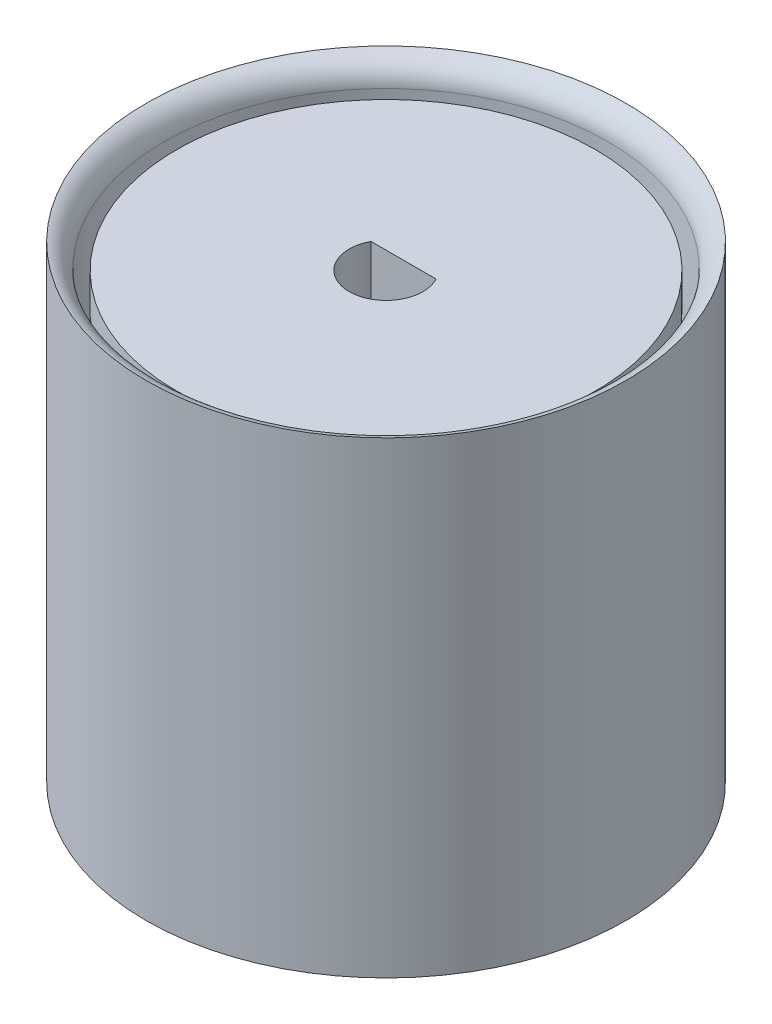
SolidWorks part; units mm, degrees
ref_plane "Front Plane" through (0, 0, 0) normal (0, 0, 1) x (1, 0, 0)
ref_plane "Top Plane" through (0, 0, 0) normal (0, 1, 0) x (1, 0, 0)
ref_plane "Right Plane" through (0, 0, 0) normal (1, 0, 0) x (0, 0, -1)
ref_plane "Plane1" through (0, -15, 0) normal (0, 1, 0) x (1, 0, 0)
ref_plane "Plane2" through (0, 21, 0) normal (0, 1, 0) x (1, 0, 0)
sketch "Sketch1" plane through (0, -15, 0) normal (0, 1, 0) x (1, 0, 0)
  circle A0 centre (0, 0) radius 17
  dimension "D1" = 34
extrude "Boss-Extrude1" add sketch "Sketch1" along normal blind 3
sketch "Sketch3" plane through (0, 21, 0) normal (0, 1, 0) x (1, 0, 0)
  circle A0 centre (0, 0) radius 17
  dimension "D1" = 34
extrude "Boss-Extrude2" add sketch "Sketch3" against normal blind 3 separate body
ref_plane "Plane3" through (0, -12, 0) normal (0, 1, 0) x (1, 0, 0)
sketch "Sketch6" plane through (0, -12, 0) normal (0, 1, 0) x (1, 0, 0)
  line L0 (-10.3961, -6.8606) -> (-11.6878, -8.1522)
  line L1 (-11.6878, -8.1522) -> (-12.2448, -7.2889)
  line L2 (-12.2448, -7.2889) -> (-12.7381, -6.3877)
  line L3 (-12.7381, -6.3877) -> (-13.1653, -5.4532)
  line L4 (-13.1653, -5.4532) -> (-13.524, -4.4905)
  line L5 (-13.524, -4.4905) -> (-13.8124, -3.5043)
  line L6 (-13.8124, -3.5043) -> (-14.029, -2.5)
  line L7 (-14.029, -2.5) -> (-12.2023, -2.5)
  line L8 (-12.2023, -2.5) -> (-12.2023, 2.5)
  line L9 (-12.2023, 2.5) -> (-14.029, 2.5)
  line L10 (-14.029, 2.5) -> (-13.8124, 3.5043)
  line L11 (-13.8124, 3.5043) -> (-13.524, 4.4905)
  line L12 (-13.524, 4.4905) -> (-13.1653, 5.4532)
  line L13 (-13.1653, 5.4532) -> (-12.7381, 6.3877)
  line L14 (-12.7381, 6.3877) -> (-12.2448, 7.2889)
  line L15 (-12.2448, 7.2889) -> (-11.6878, 8.1522)
  line L16 (-11.6878, 8.1522) -> (-10.3961, 6.8606)
  line L17 (-10.3961, 6.8606) -> (-6.8606, 10.3961)
  line L18 (-6.8606, 10.3961) -> (-8.1522, 11.6878)
  line L19 (-8.1522, 11.6878) -> (-7.2889, 12.2448)
  line L20 (-7.2889, 12.2448) -> (-6.3877, 12.7381)
  line L21 (-6.3877, 12.7381) -> (-5.4532, 13.1653)
  line L22 (-5.4532, 13.1653) -> (-4.4905, 13.524)
  line L23 (-4.4905, 13.524) -> (-3.5043, 13.8124)
  line L24 (-3.5043, 13.8124) -> (-2.5, 14.029)
  line L25 (-2.5, 14.029) -> (-2.5, 12.1742)
  line L26 (-2.5, 12.1742) -> (2.5, 12.2023)
  line L27 (2.5, 12.2023) -> (2.5, 14.029)
  line L28 (2.5, 14.029) -> (3.5043, 13.8124)
  line L29 (3.5043, 13.8124) -> (4.4905, 13.524)
  line L30 (4.4905, 13.524) -> (5.4532, 13.1653)
  line L31 (5.4532, 13.1653) -> (6.3877, 12.7381)
  line L32 (6.3877, 12.7381) -> (7.2889, 12.2448)
  line L33 (7.2889, 12.2448) -> (8.1522, 11.6878)
  line L34 (8.1522, 11.6878) -> (6.8606, 10.3961)
  line L35 (6.8606, 10.3961) -> (10.3961, 6.8606)
  line L36 (10.3961, 6.8606) -> (11.6878, 8.1522)
  line L37 (11.6878, 8.1522) -> (12.2448, 7.2889)
  line L38 (12.2448, 7.2889) -> (12.7381, 6.3877)
  line L39 (12.7381, 6.3877) -> (13.1653, 5.4532)
  line L40 (13.1653, 5.4532) -> (13.524, 4.4905)
  line L41 (13.524, 4.4905) -> (13.8124, 3.5043)
  line L42 (13.8124, 3.5043) -> (14.029, 2.5)
  line L43 (14.029, 2.5) -> (12.2023, 2.5)
  line L44 (12.2023, 2.5) -> (12.2023, -2.5)
  line L45 (12.2023, -2.5) -> (14.029, -2.5)
  line L46 (14.029, -2.5) -> (13.8124, -3.5043)
  line L47 (13.8124, -3.5043) -> (13.524, -4.4905)
  line L48 (13.524, -4.4905) -> (13.1653, -5.4532)
  line L49 (13.1653, -5.4532) -> (12.7381, -6.3877)
  line L50 (12.7381, -6.3877) -> (12.2448, -7.2889)
  line L51 (12.2448, -7.2889) -> (11.6878, -8.1522)
  line L52 (11.6878, -8.1522) -> (10.3961, -6.8606)
  line L53 (10.3961, -6.8606) -> (6.8606, -10.3961)
  line L54 (6.8606, -10.3961) -> (8.1522, -11.6878)
  line L55 (8.1522, -11.6878) -> (7.2889, -12.2448)
  line L56 (7.2889, -12.2448) -> (6.3877, -12.7381)
  line L57 (6.3877, -12.7381) -> (5.4532, -13.1653)
  line L58 (5.4532, -13.1653) -> (4.4905, -13.524)
  line L59 (4.4905, -13.524) -> (3.5043, -13.8124)
  line L60 (3.5043, -13.8124) -> (2.5, -14.029)
  line L61 (2.5, -14.029) -> (2.5, -12.2023)
  line L62 (2.5, -12.2023) -> (-2.5, -12.2023)
  line L63 (-2.5, -12.2023) -> (-2.5, -14.029)
  line L64 (-2.5, -14.029) -> (-3.5043, -13.8124)
  line L65 (-3.5043, -13.8124) -> (-4.4905, -13.524)
  line L66 (-4.4905, -13.524) -> (-5.4532, -13.1653)
  line L67 (-5.4532, -13.1653) -> (-6.3877, -12.7381)
  line L68 (-6.3877, -12.7381) -> (-7.2889, -12.2448)
  line L69 (-7.2889, -12.2448) -> (-8.1522, -11.6878)
  line L70 (-8.1522, -11.6878) -> (-6.8606, -10.3961)
  line L71 (-6.8606, -10.3961) -> (-10.3961, -6.8606)
extrude "Boss-Extrude3" add sketch "Sketch6" along normal blind 31
sketch "Sketch7" plane through (-0.0686, 0, -12.1878) normal (-0.0056, 0, -1) x (-1, 0, 0.0056)
  circle A0 centre (-0.1208, 1.3063) radius 1.7514
extrude "Cut-Extrude11" cut sketch "Sketch7" against normal blind 50 and the other way blind 60
sketch "Sketch2" plane through (0, -15, 0) normal (0, 1, 0) x (1, 0, 0)
  line L0 (2.6423, 1.4206) -> (-2.6423, 1.4206)
  arc A0 (2.6423, 1.4206) -> (-2.6423, 1.4206) centre (0, 0) cw
extrude "Cut-Extrude1" cut sketch "Sketch2" along normal blind 50
sketch "Sketch8" plane through (0, -15, 0) normal (0, 1, 0) x (1, 0, 0)
  line L1 (-3.9871, 11.5054) -> (3.5129, 11.5054)
  line L2 (-3.9871, 11.5054) -> (-3.9871, 9.5054)
  line L3 (-3.9871, 9.5054) -> (3.5129, 9.5054)
  line L4 (3.5129, 11.5054) -> (3.5129, 9.5054)
  dimension "D1" = 7.5
  dimension "D2" = 2
  dimension "D3" = 2
extrude "Cut-Extrude12" cut sketch "Sketch8" along normal blind 30
ref_plane "Plane4" through (0, 0, 0) normal (0, 0, 1) x (1, 0, 0)
mirror "Mirror1" about plane through (0, 0, 0) normal (0, 0, 1) of "Cut-Extrude12"
ref_plane "Plane5" through (0, 0, 0) normal (1, 0, 0) x (0, 0, -1)
sketch "Sketch9" plane through (0, -15, 0) normal (0, 1, 0) x (1, 0, 0)
  circle A2 centre (0, 0) radius 19.5
  circle A4 centre (0, 0) radius 18
  dimension "D1" = 36
  dimension "38" = 39
extrude "Boss-Extrude4" add sketch "Sketch9" along normal blind 38
fillet "Fillet1" radius 2 1 edges at (0, 23, 18)
sketch "Sketch10" plane through (0, -15, 0) normal (0, 1, 0) x (1, 0, 0)
  circle A0 centre (0, 0) radius 19.5
  circle A1 centre (0, 0) radius 17
extrude "Boss-Extrude5" add sketch "Sketch10" along normal blind 3
